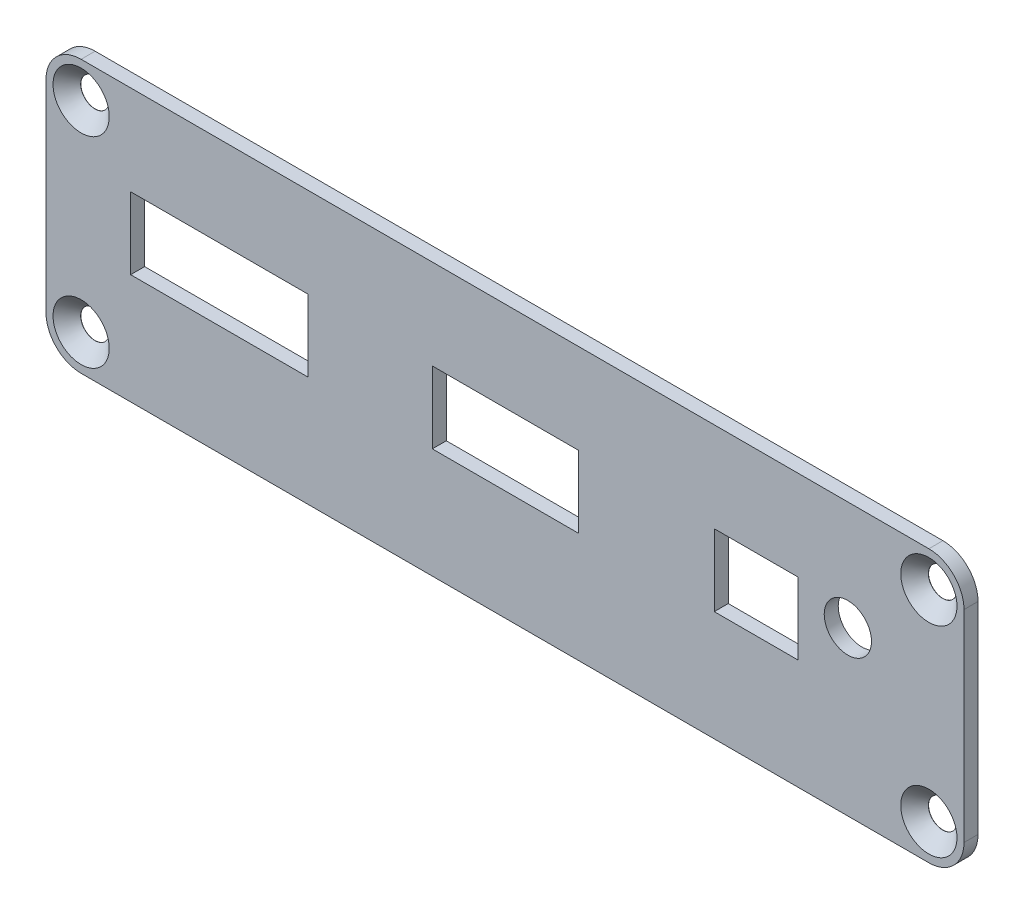
SolidWorks part; units mm, degrees
ref_plane "Front Plane" through (0, 0, 0) normal (0, 0, 1) x (1, 0, 0)
ref_plane "Top Plane" through (0, 0, 0) normal (0, 1, 0) x (1, 0, 0)
ref_plane "Right Plane" through (0, 0, 0) normal (1, 0, 0) x (0, 0, -1)
sketch "Sketch1" plane through (0, 0, 0) normal (0, 0, 1) x (1, 0, 0)
  line L1 (0, 0) -> (102.87, 0)
  line L2 (0, 0) -> (0, 30.48)
  line L3 (0, 30.48) -> (102.87, 30.48)
  line L4 (102.87, 0) -> (102.87, 30.48)
  dimension "D1" = 102.87
  dimension "D2" = 30.48
extrude "Boss-Extrude1" add sketch "Sketch1" along normal blind 1.57
fillet "Fillet1" radius 3.935 4 edges at (0, 0, 0.785) (102.87, 0, 0.785) (102.87, 30.48, 0.785) (0, 30.48, 0.785)
hole_wizard "CSK for M3 Flat Head Machine Screw1" positions "Sketch3" profile "Sketch4" countersink size "M3" standard "ANSI Metric" end condition through all
sketch "Sketch3" plane through (0, 0, 1.57) normal (0, 0, 1) x (1, 0, 0)
  line L0 (0, 26.545) -> (0, 3.935) construction
  line L1 (98.935, 30.48) -> (3.935, 30.48) construction
  line L2 (3.935, 0) -> (98.935, 0) construction
  line L3 (102.87, 3.935) -> (102.87, 26.545) construction
  point P0 (3.937, 26.4795)
  point P8 (3.937, 4.0005)
  point P10 (98.933, 26.4795)
  point P12 (98.933, 4.0005)
  dimension "D1" = 3.937
  dimension "D2" = 4.0005
  dimension "D3" = 3.937
  dimension "D4" = 4.0005
  dimension "D5" = 3.937
  dimension "D6" = 4.0005
  dimension "D7" = 4.0005
  dimension "D8" = 3.937
sketch "Sketch4" plane through (3.937, 26.4795, 1.57) normal (1, 0, 0) x (0, -1, 0)
  line L0 (0, 0) -> (0, 1.57)
  line L1 (0, 1.57) -> (1.6, 1.57)
  line L2 (1.6, 1.57) -> (1.6, 1.55)
  line L3 (1.6, 1.55) -> (3.15, 0)
  line L5 (3.15, 0) -> (0, 0)
  line L6 (-1.6, 1.55) -> (-3.15, 0) construction
  line L11 (0, -6.35) -> (0, 107.95) construction
  dimension "Thru Hole Dia." = 3.2
  dimension "Thru Hole Depth" = 1.57
  dimension "Near C'Sink Dia." = 6.3
  dimension "Near C'Sink Angle" = 90
sketch "PCB" plane through (0, 0, 1.57) normal (0, 0, 1) x (1, 0, 0)
  line L0 (1.435, 10.7795) -> (0, 10.7795) construction
  line L1 (1.435, 10.7795) -> (101.435, 10.7795) construction
  line L2 (1.435, 10.7795) -> (1.435, 12.3495) construction
  line L3 (1.435, 12.3495) -> (101.435, 12.3495) construction
  line L4 (101.435, 10.7795) -> (101.435, 12.3495) construction
  line L5 (0, 26.545) -> (0, 3.935) construction
  line L6 (101.435, 10.7795) -> (102.87, 10.7795) construction
  line L7 (102.87, 3.935) -> (102.87, 26.545) construction
  line L9 (75.385, 19.8995) -> (83.785, 19.8995)
  line L10 (75.385, 19.8995) -> (75.385, 12.3495)
  line L11 (75.385, 12.3495) -> (83.785, 12.3495)
  line L12 (83.785, 19.8995) -> (83.785, 12.3495)
  line L13 (43.79, 19.8995) -> (59.19, 19.8995)
  line L14 (43.79, 19.8995) -> (43.79, 12.3495)
  line L15 (43.79, 12.3495) -> (59.19, 12.3495)
  line L16 (59.19, 19.8995) -> (59.19, 12.3495)
  line L17 (9.985, 12.3495) -> (28.885, 12.3495)
  line L18 (9.985, 12.3495) -> (9.985, 19.8995)
  line L19 (9.985, 19.8995) -> (28.885, 19.8995)
  line L20 (28.885, 12.3495) -> (28.885, 19.8995)
  circle A0 centre (89.8563, 18.264) radius 2.15
  dimension "D4" = 5.9145
  dimension "D5" = 11.5787
  dimension "D6" = 4.3
  dimension "D1" = 10.7795
  dimension "D2" = 1.57
  dimension "D3" = 100
  dimension "D7" = 8.4
  dimension "D8" = 7.55
  dimension "D9" = 17.65
  dimension "D10" = 15.4
  dimension "D11" = 18.9
  dimension "D12" = 42.245
  dimension "D13" = 72.55
sketch "Sketch6" plane through (0, 0, 1.57) normal (0, 0, 1) x (1, 0, 0)
  line L0 (75.385, 19.8995) -> (75.385, 12.3495) construction
  line L1 (75.385, 12.3495) -> (83.785, 12.3495) construction
  line L2 (83.785, 19.8995) -> (83.785, 12.3495) construction
  line L3 (75.385, 19.8995) -> (83.785, 19.8995) construction
  line L4 (59.19, 19.8995) -> (59.19, 12.3495) construction
  line L5 (43.79, 12.3495) -> (59.19, 12.3495) construction
  line L6 (43.79, 19.8995) -> (43.79, 12.3495) construction
  line L7 (43.79, 19.8995) -> (59.19, 19.8995) construction
  line L8 (9.985, 12.3495) -> (9.985, 19.8995) construction
  line L9 (9.985, 12.3495) -> (28.885, 12.3495) construction
  line L10 (28.885, 12.3495) -> (28.885, 19.8995) construction
  line L11 (9.985, 19.8995) -> (28.885, 19.8995) construction
  line L12 (75.385, 19.8995) -> (75.385, 12.3495)
  line L13 (75.385, 12.3495) -> (83.785, 12.3495)
  line L14 (83.785, 19.8995) -> (83.785, 12.3495)
  line L15 (75.385, 19.8995) -> (83.785, 19.8995)
  line L16 (59.19, 19.8995) -> (59.19, 12.3495)
  line L17 (43.79, 12.3495) -> (59.19, 12.3495)
  line L18 (43.79, 19.8995) -> (43.79, 12.3495)
  line L19 (43.79, 19.8995) -> (59.19, 19.8995)
  line L20 (9.985, 12.3495) -> (9.985, 19.8995)
  line L21 (9.985, 12.3495) -> (28.885, 12.3495)
  line L22 (28.885, 12.3495) -> (28.885, 19.8995)
  line L23 (9.985, 19.8995) -> (28.885, 19.8995)
  circle A0 centre (89.8563, 18.264) radius 2.15 construction
  circle A1 centre (89.8563, 18.264) radius 2.15
extrude "Cut-Extrude1" cut sketch "Sketch6" against normal through all
other "Move Face1" flip direction yes face at (92.0063, 18.264, 0) face at (19.435, 19.8995, 0.785) face at (51.49, 19.8995, 0.785) face at (79.585, 19.8995, 0.785) face at (75.385, 16.1245, 0.785) face at (83.785, 16.1245, 0.785) face at (59.19, 16.1245, 0.785) face at (28.885, 16.1245, 0.785) face at (9.985, 16.1245, 0.785) face at (43.79, 16.1245, 0.785) offset 0.5 parameters "D1"=0.5
equation "\"D3@Sketch3\"=\"D1@Sketch3\""
equation "\"D4@Sketch3\"=\"D2@Sketch3\""
equation "\"D5@Sketch3\"=\"D1@Sketch3\""
equation "\"D6@Sketch3\"=\"D2@Sketch3\""
equation "\"D7@Sketch3\"=\"D2@Sketch3\""
equation "\"D8@Sketch3\"=\"D1@Sketch3\""
